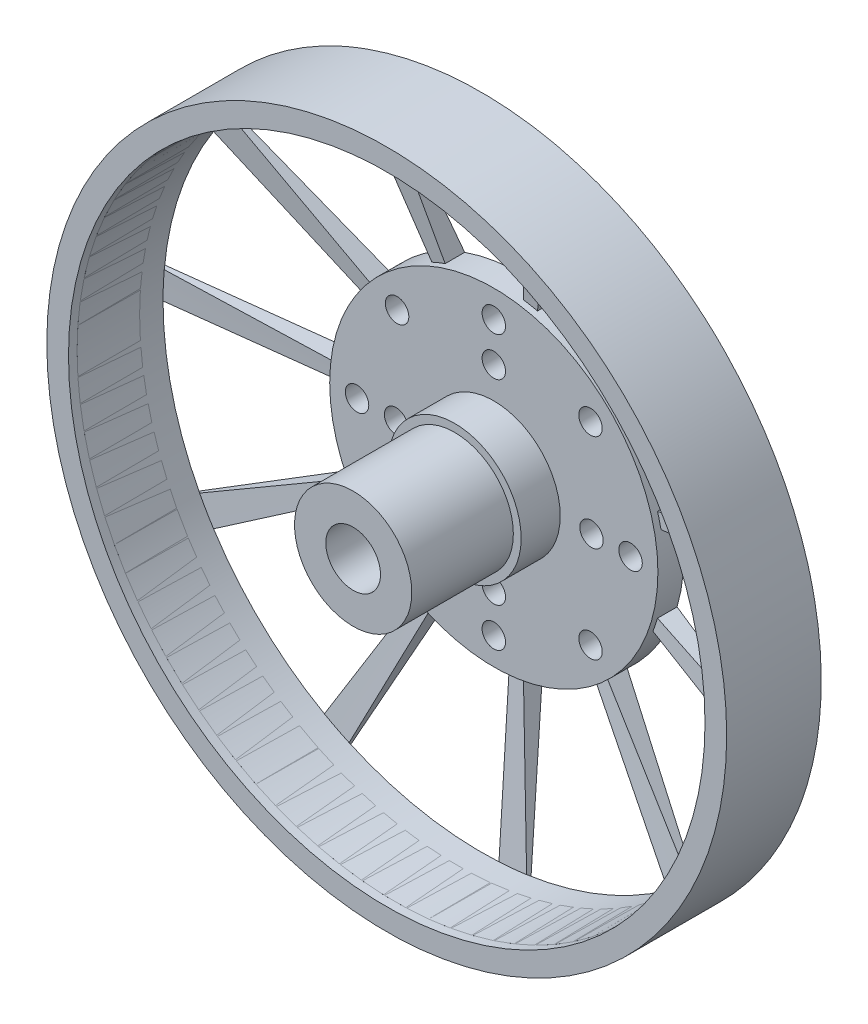
SolidWorks part; units mm, degrees
note: The reader was unsure of these and kept them because the rebuilt part matched: shared geometry of "Sketch1<4>".
ref_plane "Front Plane" through (0, 0, 0) normal (0, 0, 1) x (1, 0, 0)
ref_plane "Top Plane" through (0, 0, 0) normal (0, 1, 0) x (1, 0, 0)
ref_plane "Right Plane" through (0, 0, 0) normal (1, 0, 0) x (0, 0, -1)
sketch "Sketch1" plane through (0, 0, 0) normal (0, 0, 1) x (1, 0, 0)
  circle A0 centre (0, 0) radius 40.725
  circle A1 centre (0, 0) radius 43.5
  circle A2 centre (0, 0) radius 21
  circle A3 centre (0, 0) radius 7.5
  circle A4 centre (0, 0) radius 5.25
  dimension "D1" = 81.45
  dimension "D2" = 87
  dimension "D3" = 42
  dimension "D4" = 15
  dimension "D5" = 10.5
extrude "Boss-Extrude1" add sketch "Sketch1" along normal blind 12.1 from offset 4.9 contours A1 A0
extrude "Boss-Extrude2" add sketch "Sketch1<4>" along normal blind 3.3 separate body contours A2 A3 | A3 A4
sketch "Sketch1<4>" plane through (0, 0, 0) normal (0, 0, 1) x (1, 0, 0) same geometry as "Sketch1"
sketch "Sketch2" plane through (0, 0, 0) normal (0, 1, 0) x (1, 0, 0)
  line L0 (21, 0) -> (-21, 0) construction
  line L1 (43.5, -4.9) -> (-43.5, -4.9) construction
  line L2 (21, 0) -> (-21, 0)
  line L3 (43.5, -4.9) -> (-43.5, -4.9)
  line L4 (-43.5, -4.9) -> (-21, 0)
  line L5 (-21, 0) -> (-21, -3.3) construction
  line L6 (40.725, -4.9) -> (-40.725, -4.9) construction
  line L7 (-21, 0) -> (-21, -3.3)
  line L8 (40.725, -4.9) -> (-40.725, -4.9)
  line L9 (-40.725, -4.9) -> (-21, -2.5)
  dimension "D1" = 2.5
ref_axis "Axis1" through (0, 0, 3.3) along (0, 0, -1)
revolve "Revolve1" add sketch "Sketch2" angle 5 about axis through (0, 0, 3.3) along (0, 0, -1)
pattern_circular "CirPattern1" count 11 over 360 about axis through (0, 0, 0) along (0, 0, 1) of "Revolve1"
sketch "Sketch3" plane through (0, 0, 3.3) normal (0, 0, 1) x (1, 0, 0)
  circle A0 centre (0, 0) radius 7.5
  circle A1 centre (0, 0) radius 3.5
  dimension "D1" = 15
  dimension "D2" = 7
extrude "Boss-Extrude3" add sketch "Sketch3" along normal blind 18
sketch "Sketch4" plane through (0, 0, 3.3) normal (0, 0, 1) x (1, 0, 0)
  circle A0 centre (0, 0) radius 8.5
  circle A1 centre (0, 0) radius 3.5
  dimension "D1" = 17
extrude "Boss-Extrude4" add sketch "Sketch4" along normal blind 5
sketch "Sketch6" plane through (0, 0, 0) normal (0, 0, -1) x (-1, 0, 0)
  circle A0 centre (0, 0) radius 17.5 construction
  circle A1 centre (0, 0) radius 12.5 construction
  circle A2 centre (0, 12.5) radius 1.5
  circle A3 centre (12.5, 0) radius 1.5
  circle A4 centre (0, -12.5) radius 1.5
  circle A5 centre (-12.5, 0) radius 1.5
  circle A6 centre (0, 17.5) radius 1.5
  circle A7 centre (12.3744, 12.3744) radius 1.5
  circle A8 centre (17.5, 0) radius 1.5
  circle A9 centre (12.3744, -12.3744) radius 1.5
  circle A10 centre (0, -17.5) radius 1.5
  circle A11 centre (-12.3744, -12.3744) radius 1.5
  circle A12 centre (-17.5, 0) radius 1.5
  circle A13 centre (-12.3744, 12.3744) radius 1.5
  point P15 (0, 0)
  point P31 (0, 0)
  dimension "D1" = 35
  dimension "D2" = 25
  dimension "D3" = 3
  dimension "D5" = 3
  dimension "D4" = 4
  dimension "D6" = 8
extrude "Cut-Extrude1" cut sketch "Sketch6" against normal blind 5
sketch "Sketch7" plane through (0, 0, 17) normal (0, 0, 1) x (1, 0, 0)
  circle A0 centre (0, 0) radius 40.725
  circle A1 centre (0, 0) radius 43.25
  dimension "D1" = 86.5
extrude "Boss-Extrude5" add sketch "Sketch7" against normal blind 8 from offset 1.1 separate body offset against normal yes
